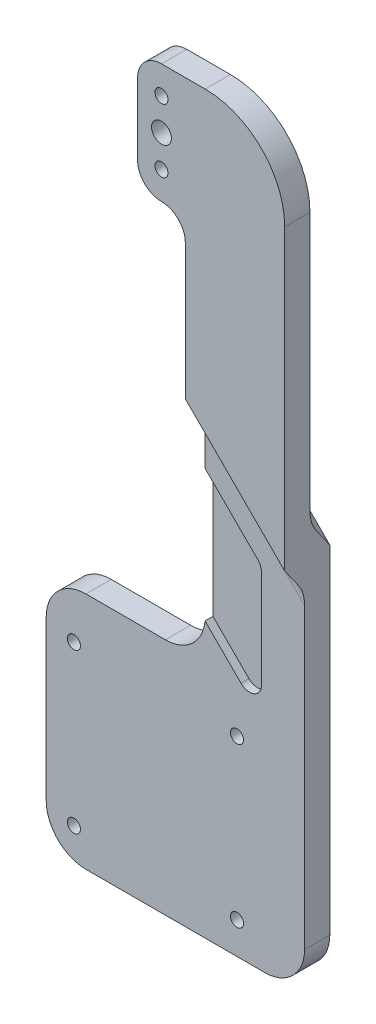
SolidWorks part; units mm, degrees
ref_plane "Front Plane" through (0, 0, 0) normal (0, 0, 1) x (1, 0, 0)
ref_plane "Top Plane" through (0, 0, 0) normal (0, 1, 0) x (1, 0, 0)
ref_plane "Right Plane" through (0, 0, 0) normal (1, 0, 0) x (0, 0, -1)
sketch "Sketch1" plane through (0, 0, 0) normal (0, 0, 1) x (1, 0, 0)
  line L1 (-6, -15) -> (6, -15)
  line L2 (-6, -15) -> (-6, 15)
  line L3 (-6, 15) -> (6, 15)
  line L4 (6, -15) -> (6, 15)
  line L5 (-6, -15) -> (6, 15) construction
  line L6 (-6, 15) -> (6, -15) construction
  line L7 (6, 15) -> (31, 15)
  line L8 (6, 15) -> (6, -175)
  line L9 (6, -175) -> (31, -175)
  line L10 (31, 15) -> (31, -175)
  circle A0 centre (0, 8) radius 1.65
  circle A1 centre (0, 0) radius 2.5
  circle A2 centre (0, -8) radius 1.65
  dimension "D1" = 3.3
  dimension "D2" = 5
  dimension "D4" = 3.3
  dimension "D3" = 8
  dimension "D5" = 8
  dimension "D6" = 30
  dimension "D7" = 12
  dimension "D8" = 190
  dimension "D9" = 25
extrude "Boss-Extrude1" add sketch "Sketch1" along normal blind 6.35 contours L10 L7 L4 L8 L9 | L1 L4 L3 L2 A2 A1 A0
fillet "Fillet1" radius 6 2 edges at (6, -15, 3.175) (-6, -15, 3.175)
fillet "Fillet2" radius 6 1 edges at (-6, 15, 3.175)
fillet "Fillet3" radius 20 1 edges at (31, 15, 3.175)
sketch "Sketch2" plane through (0, 0, 6.35) normal (0, 0, 1) x (1, 0, 0)
  line L0 (6, -175) -> (31, -175) construction
  line L1 (6, -175) -> (6, -21) construction
  circle A0 centre (14, -167) radius 1.65
  circle A2 centre (14, -127) radius 1.65
  dimension "D1" = 3.3
  dimension "D2" = 3.3
  dimension "D3" = 40
  dimension "D4" = 8
  dimension "D5" = 8
extrude "Cut-Extrude1" cut sketch "Sketch2" against normal blind 10
sketch "Sketch3" plane through (0, 0, 6.35) normal (0, 0, 1) x (1, 0, 0)
  line L1 (31, -80) -> (6, -55)
  line L5 (31, -175) -> (31, -5)
  line L6 (11, 15) -> (0, 15)
  line L7 (-6, 9) -> (-6, -9)
  line L8 (6, -21) -> (6, -175)
  line L9 (6, -175) -> (31, -175)
  line L10 (31, -175) -> (31, -5)
  line L11 (11, 15) -> (0, 15)
  line L12 (-6, 9) -> (-6, -9)
  line L13 (6, -21) -> (6, -175)
  line L14 (6, -175) -> (31, -175)
  arc A4 (31, -5) -> (11, 15) centre (11, -5) ccw
  arc A5 (0, 15) -> (-6, 9) centre (0, 9) ccw
  arc A6 (-6, -9) -> (0, -15) centre (0, -9) ccw
  arc A7 (6, -21) -> (0, -15) centre (0, -21) ccw
  arc A8 (31, -5) -> (11, 15) centre (11, -5) ccw
  arc A9 (0, 15) -> (-6, 9) centre (0, 9) ccw
  arc A10 (-6, -9) -> (0, -15) centre (0, -9) ccw
  arc A11 (6, -21) -> (0, -15) centre (0, -21) ccw
  dimension "D1" = 0
extrude "Cut-Extrude3" cut sketch "Sketch3" against normal blind 5
sketch "Sketch5" plane through (0, 0, 0) normal (0, 0, -1) x (-1, 0, 0)
  line L4 (-6, -55) -> (-31, -80)
  line L5 (-6, -175) -> (-6, -55)
  line L6 (-31, -175) -> (-6, -175)
  line L7 (-31, -80) -> (-31, -175)
  line L9 (-6, -175) -> (-6, -55)
  line L10 (-31, -175) -> (-6, -175)
  line L11 (-31, -80) -> (-31, -175)
  line L13 (-6, -55) -> (-31, -80)
  dimension "D1" = 0
extrude "Boss-Extrude3" add sketch "Sketch5" along normal blind 5
chamfer "Chamfer2" distance 5 angle 45 2 edges at (18.5, -67.5, 1.35) (18.5, -67.5, 0)
fillet "Fillet5" radius 5 2 edges at (18.5, -60.4289, 0) (18.5, -74.5711, 1.35)
sketch "Sketch6" plane through (0, 0, 1.35) normal (0, 0, 1) x (1, 0, 0)
  circle A0 centre (14, -127) radius 1.65 construction
  circle A1 centre (14, -167) radius 1.65 construction
  circle A2 centre (14, -127) radius 1.65
  circle A3 centre (14, -167) radius 1.65
extrude "Cut-Extrude4" cut sketch "Sketch6" against normal through all
sketch "Sketch7" plane through (0, 0, 1.35) normal (0, 0, 1) x (1, 0, 0)
  line L0 (6, -105.9405) -> (20.1421, -120.0826)
  line L1 (6, -65) -> (6, -175) construction
  line L2 (20.1421, -120.0826) -> (20.1421, -86.8281)
  line L3 (20.1421, -86.8281) -> (6, -72.6859)
  dimension "D1" = 20
extrude "Cut-Extrude5" cut sketch "Sketch7" against normal blind 2 and the other way through all
fillet "Fillet6" radius 3 2 edges at (20.1421, -86.8281, 0.35) (20.1421, -120.0826, 0.35)
sketch "Sketch8" plane through (0, 0, 1.35) normal (0, 0, 1) x (1, 0, 0)
  line L1 (6, -175) -> (-34, -175)
  line L2 (6, -175) -> (6, -115)
  line L3 (6, -115) -> (-34, -115)
  line L4 (-34, -175) -> (-34, -115)
  circle A0 centre (-27.0316, -127) radius 1.65
  circle A1 centre (-27.0316, -167) radius 1.65
  dimension "D3" = 3.3
  dimension "D4" = 3.3
  dimension "D1" = 60
  dimension "D2" = 40
extrude "Boss-Extrude4" add sketch "Sketch8" against normal up to surface (6.35 mm away) up to face at (15.65, -127, -5)
fillet "Fillet7" radius 10 4 edges at (6, -115, -1.825) (31, -175, -1.825) (-34, -175, -1.825) (-34, -115, -1.825)
